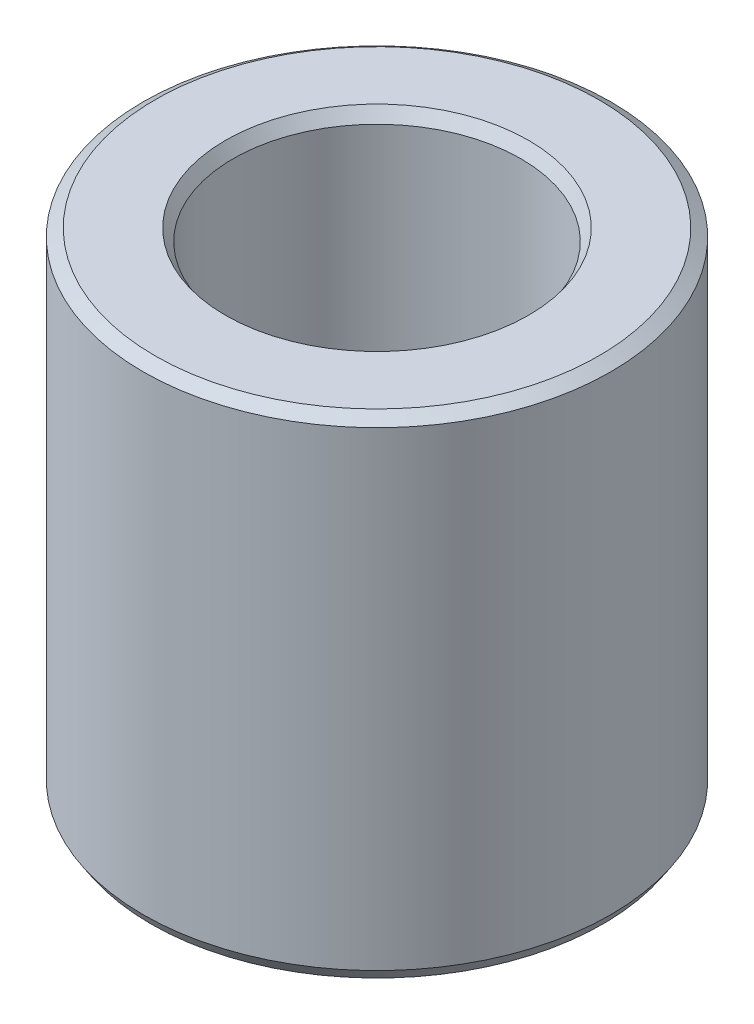
SolidWorks part; units mm, degrees
ref_plane "Front Plane" through (0, 0, 0) normal (0, 0, 1) x (1, 0, 0)
ref_plane "Top Plane" through (0, 0, 0) normal (0, 1, 0) x (1, 0, 0)
ref_plane "Right Plane" through (0, 0, 0) normal (1, 0, 0) x (0, 0, -1)
sketch "Sketch1" plane through (0, 0, 0) normal (0, 1, 0) x (1, 0, 0)
  circle A0 centre (0, 0) radius 57.5
  dimension "SLEEVE_OD" = 115
extrude "Boss-Extrude1" add sketch "Sketch1" along normal blind 120.4666
sketch "Sketch2" plane through (0, 0, 0) normal (0, 1, 0) x (1, 0, 0)
  circle A0 centre (0, 0) radius 35.3546
  dimension "BORE_D" = 70.7093
extrude "Cut-Extrude1" cut sketch "Sketch2" along normal through all
chamfer "Chamfer1" distance 1.9149 angle 56.947 4 edges at (0, 120.4666, 35.3546) (0, 0, 35.3546) (0, 0, 57.5) (0, 120.4666, 57.5) first distance on face at (0, 120.4666, 35.3546) first distance on face at (0, 0, 35.3546) first distance on face at (0, 120.4666, 57.5)
